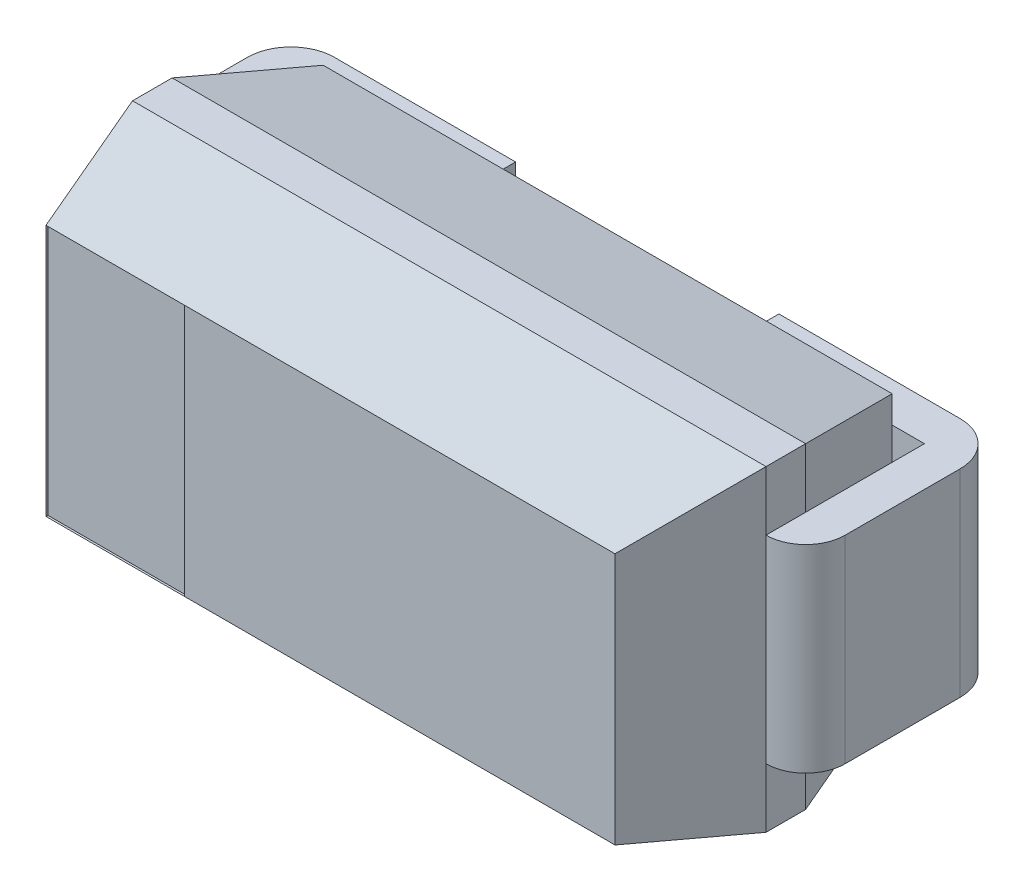
SolidWorks part; units mm, degrees
other "Детальный элемент1"
ref_plane "Спереди" through (0, 0, 0) normal (0, 0, 1) x (1, 0, 0)
ref_plane "Сверху" through (0, 0, 0) normal (0, 1, 0) x (1, 0, 0)
ref_plane "Справа" through (0, 0, 0) normal (1, 0, 0) x (0, 0, -1)
ref_plane "Плоскость1" through (0, 0, 0.2) normal (0, 0, 1) x (1, 0, 0)
sketch "Эскиз1" plane through (0, 0, 0.2) normal (0, 0, 1) x (1, 0, 0)
  line L1 (-1.6, 0.8) -> (1.6, 0.8)
  line L2 (-1.6, 0.8) -> (-1.6, -0.8)
  line L3 (-1.6, -0.8) -> (1.6, -0.8)
  line L4 (1.6, 0.8) -> (1.6, -0.8)
  line L5 (-1.6, 0.8) -> (1.6, -0.8) construction
  line L6 (-1.6, -0.8) -> (1.6, 0.8) construction
  point P0 (0, 0)
  dimension "D1" = 3.2
  dimension "D2" = 1.6
extrude "Бобышка-Вытянуть1" add sketch "Эскиз1" along normal blind 1.4
chamfer "Фаска1" distance 0.6 distance2 0.163 4 edges at (0, 0.8, 1.6) (1.6, 0, 1.6) (0, -0.8, 1.6) (-1.6, 0, 1.6) first distance on face at (0, 0.8, 0.9) first distance on face at (1.6, 0, 0.9) first distance on face at (0, -0.8, 0.9) first distance on face at (-1.6, 0, 0.9)
chamfer "Фаска2" distance 0.163 distance2 0.6 4 edges at (1.6, 0, 0.2) (0, 0.8, 0.2) (0, -0.8, 0.2) (-1.6, 0, 0.2) first distance on face at (0, 0, 0.2)
sketch "Эскиз2" plane through (0, 0, 0) normal (0, 1, 0) x (1, 0, 0)
  line L0 (-1.6, -0.2) -> (-1.6, -0.8)
  line L1 (-0.665, 0) -> (-1.58, 0)
  line L2 (-0.665, 0) -> (-0.665, -0.2)
  line L3 (-0.665, -0.2) -> (-1.6, -0.2)
  line L4 (-1.6, -0.8) -> (-1.6, -1)
  line L5 (-1.8, -0.8) -> (-1.8, -0.22)
  arc A2 (-1.6, -1) -> (-1.8, -0.8) centre (-1.6, -0.8) cw
  arc A3 (-1.58, 0) -> (-1.8, -0.22) centre (-1.58, -0.22) ccw
  dimension "D3" = 0.22
  dimension "D1" = 0.2
  dimension "D2" = 0.2
  dimension "D4" = 0.915
extrude "Бобышка-Вытянуть2" add sketch "Эскиз2" along normal blind 0.5 and the other way blind 0.5 separate body
mirror "Зеркальное отражение1" about plane through (0, 0, 0) normal (1, 0, 0) of bodies 108
sketch "Эскиз3" plane through (0, 0, 1.6) normal (0, 0, 1) x (1, 0, 0)
  line L0 (1.437, 0.637) -> (-1.437, 0.637) construction
  line L1 (-1.437, -0.637) -> (-0.737, -0.637)
  line L2 (-1.437, -0.637) -> (-1.437, 0.637)
  line L3 (-1.437, 0.637) -> (-0.737, 0.637)
  line L4 (-0.737, -0.637) -> (-0.737, 0.637)
  dimension "D1" = 0.7
extrude "Вырез-Вытянуть1" cut sketch "Эскиз3" against normal blind 0.01
